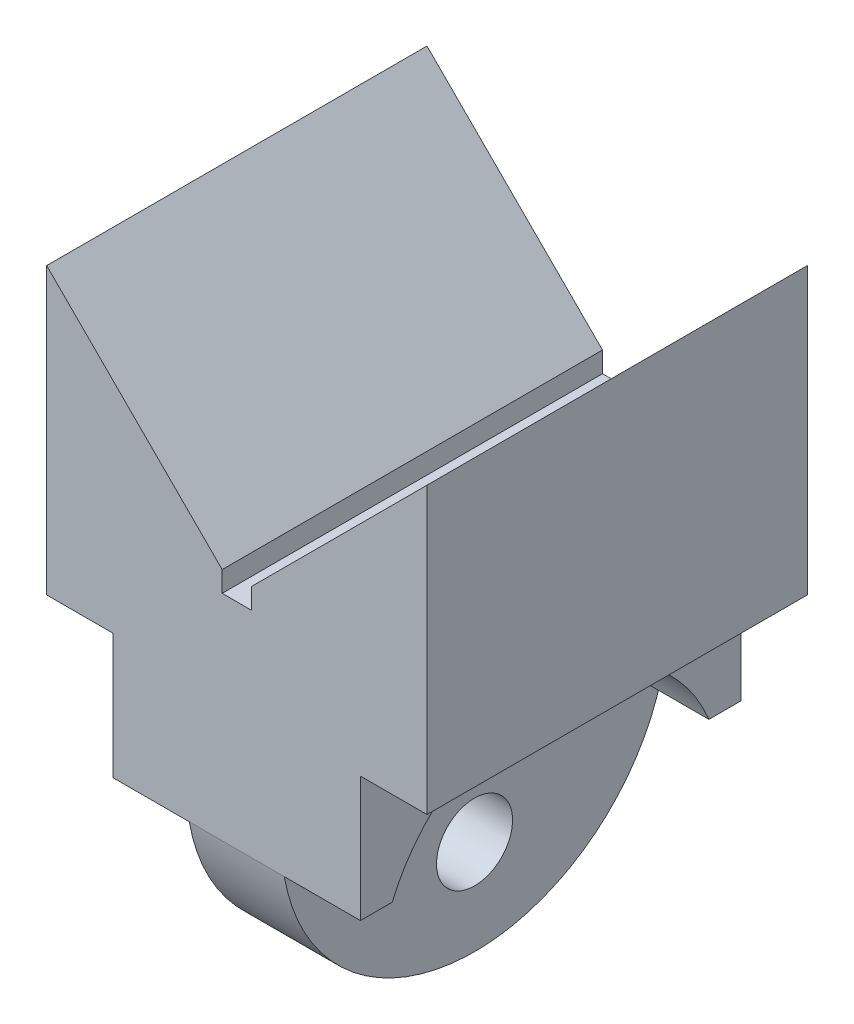
SolidWorks part; units mm, degrees
ref_plane "Alzado" through (0, 0, 0) normal (0, 0, 1) x (1, 0, 0)
ref_plane "Planta" through (0, 0, 0) normal (0, 1, 0) x (1, 0, 0)
ref_plane "Vista lateral" through (0, 0, 0) normal (1, 0, 0) x (0, 0, -1)
sketch "Croquis1" plane through (0, 0, 0) normal (0, 0, 1) x (1, 0, 0)
  line L0 (0, 0) -> (0, 109.5959) construction
  line L1 (2.5, 0) -> (-2.5, 0)
  line L2 (-2.5, 0) -> (-2.5, 15)
  line L3 (-2.5, 15) -> (-10, 15)
  line L4 (-10, 15) -> (-10, 30)
  line L5 (-10, 30) -> (-0.771, 20.771)
  line L6 (-0.771, 20.771) -> (-0.771, 19.6882)
  line L7 (-0.771, 19.6882) -> (0.771, 19.6882)
  line L8 (0.771, 20.771) -> (0.771, 19.6882)
  line L9 (10, 30) -> (0.771, 20.771)
  line L10 (10, 15) -> (10, 30)
  line L11 (2.5, 15) -> (10, 15)
  line L12 (2.5, 0) -> (2.5, 15)
  point P6 (-16.9137, 46.7939)
  point P11 (-2.8094, 39.9004)
  point P12 (-12.5, 64.732)
  point P13 (-1.3445, 18.2869)
  point P14 (-0.6931, 18.807)
  point P15 (-1.0326, 18.1845)
  point P17 (0, 19.6882)
  point P22 (0.9512, 17.9512)
  point P23 (-0.771, 16.6882)
  dimension "D1" = 45
  dimension "D2" = 15
  dimension "D3" = 7.5
  dimension "D4" = 2.5
  dimension "D5" = 15
extrude "Saliente-Extruir1" add sketch "Croquis1" along normal blind 20
sketch "Croquis2" plane through (-2.5, 0, 0) normal (-1, 0, 0) x (0, 0, 1)
  line L0 (10, 0) -> (10, 12.1435) construction
  line L1 (20, 0) -> (0, 0) construction
  circle A0 centre (10, 5) radius 2
  dimension "D1" = 4
extrude "Cortar-Extruir1" cut sketch "Croquis2" against normal through all contours A0
sketch "Croquis3" plane through (-2.5, 0, 0) normal (-1, 0, 0) x (0, 0, 1)
  line L3 (10, 5) -> (10, 15) construction
  line L4 (20, 0) -> (0, 0) construction
  line L6 (0, 8.4205) -> (0, 15)
  line L7 (0, 15) -> (20, 15)
  line L8 (20, 15) -> (20, 8.4205)
  line L9 (0, 8.4205) -> (1.6753, 8.4205)
  line L10 (18.3247, 8.4205) -> (20, 8.4205)
  line L11 (0, 5) -> (20, 5) construction
  arc A0 (1.6753, 8.4205) -> (18.3247, 8.4205) centre (10, 5) cw
  circle A3 centre (10, 5) radius 2 construction
  point P4 (10, 0)
  point P5 (1.6753, 8.4205)
  point P12 (1.1263, 9.6106)
  dimension "D1" = 9
extrude "Saliente-Extruir3" add sketch "Croquis3" along normal blind 4
ref_plane "Plano2" through (0, 0, 0) normal (-1, 0, 0) x (0, 0, 1)
mirror "Simetría2" about plane through (0, 0, 0) normal (-1, 0, 0) of "Saliente-Extruir3"
sketch "Croquis5" plane through (-2.5, 0, 0) normal (-1, 0, 0) x (0, 0, 1)
  line L0 (0, 8.4205) -> (0, 0)
  line L1 (0, 0) -> (20, 0)
  line L2 (20, 0) -> (20, 8.4205)
  line L3 (20, 8.4205) -> (19.9912, 8.2093)
  arc A0 (0, 8.4205) -> (20, 8.4205) centre (10, 10.1481) ccw
  line M3 (0, 8.4205) -> (0, 0)
  line M4 (0, 0) -> (20, 0)
  line M5 (20, 0) -> (20, 8.4205)
extrude "Cortar-Extruir3" cut sketch "Croquis5" against normal through all contours A0 M3 M4 | A0 L1 M5 region at (-2.5, 2.1231, 2.2594) region at (-2.5, 2.1231, 17.7406)
